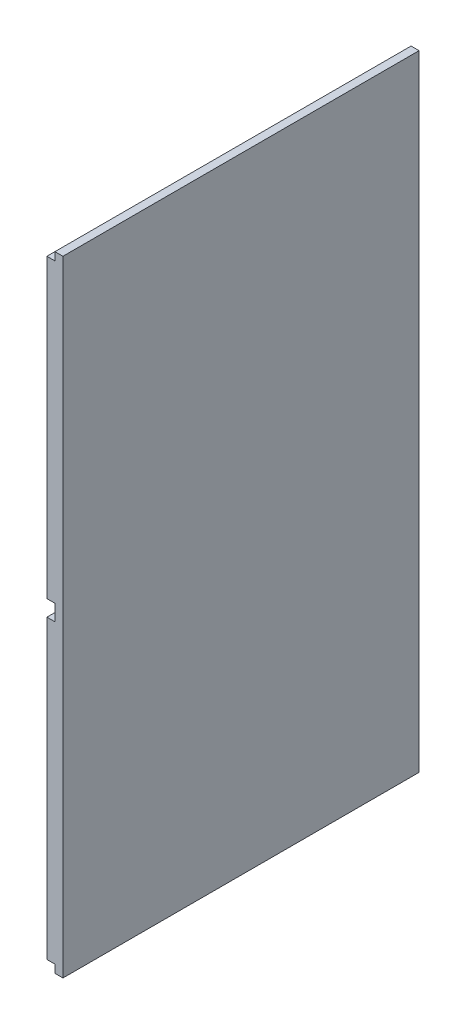
SolidWorks part; units mm, degrees
ref_plane "Front" through (0, 0, 0) normal (0, 0, 1) x (1, 0, 0)
ref_plane "Top" through (0, 0, 0) normal (0, 1, 0) x (1, 0, 0)
ref_plane "Right" through (0, 0, 0) normal (1, 0, 0) x (0, 0, -1)
sketch "Sketch1" plane through (0, 0, 0) normal (1, 0, 0) x (0, 0, -1)
  line L1 (-200, -351) -> (200, -351)
  line L2 (-200, -351) -> (-200, 351)
  line L3 (-200, 351) -> (200, 351)
  line L4 (200, -351) -> (200, 351)
  line L5 (-200, -351) -> (200, 351) construction
  line L6 (-200, 351) -> (200, -351) construction
  point P0 (0, 0)
  dimension "D1" = 400
  dimension "D2" = 702
extrude "Boss-Extrude1" add sketch "Sketch1" along normal blind 18
sketch "Sketch2" plane through (0, 0, 0) normal (-1, 0, 0) x (0, 0, 1)
  line L0 (200, 351) -> (200, -351) construction
  line L1 (-200, -351) -> (200, -351)
  line L2 (-200, -351) -> (-200, -342)
  line L3 (-200, -342) -> (200, -342)
  line L4 (200, -351) -> (200, -342)
  line L5 (-200, -351) -> (-200, 351) construction
  line L6 (200, 351) -> (-200, 351)
  line L7 (200, 351) -> (200, 342)
  line L8 (200, 342) -> (-200, 342)
  line L9 (-200, 351) -> (-200, 342)
  dimension "D1" = 9
  dimension "D2" = 9
extrude "Cut-Extrude1" cut sketch "Sketch2" against normal blind 9
sketch "Sketch3" plane through (0, 0, 0) normal (-1, 0, 0) x (0, 0, 1)
  line L0 (200, 342) -> (200, -342) construction
  line L1 (-200, -9) -> (200, -9)
  line L2 (-200, -9) -> (-200, 9)
  line L3 (-200, 9) -> (200, 9)
  line L4 (200, -9) -> (200, 9)
  line L5 (-200, -9) -> (200, 9) construction
  line L6 (-200, 9) -> (200, -9) construction
  point P0 (0, 0)
  dimension "D1" = 18
extrude "Cut-Extrude2" cut sketch "Sketch3" against normal blind 9
